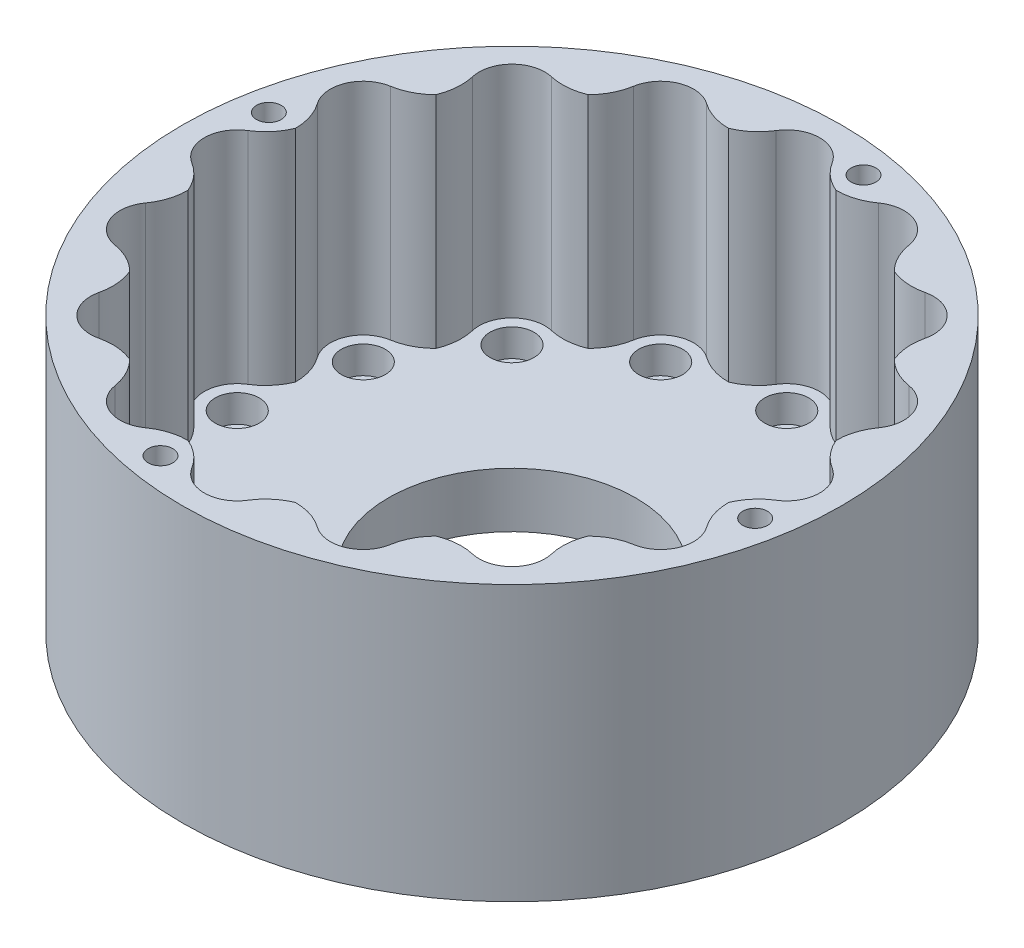
SolidWorks part; units mm, degrees
ref_plane "Front Plane" through (0, 0, 0) normal (0, 0, 1) x (1, 0, 0)
ref_plane "Top Plane" through (0, 0, 0) normal (0, 1, 0) x (1, 0, 0)
ref_plane "Right Plane" through (0, 0, 0) normal (1, 0, 0) x (0, 0, -1)
sketch "Sketch1" plane through (0, 0, 0) normal (0, 1, 0) x (1, 0, 0)
  arc A0 (-50.0283, 13.4631) -> (-51.515, 5.9892) centre (-1.875, 0) ccw
  arc A1 (4.1142, 49.64) -> (-7.8642, 49.64) centre (-1.875, 50) ccw
  arc A2 (-16.6515, 42.0695) -> (-16.6233, 42.0995) centre (-21.0092, 46.194) ccw
  arc A3 (-32.7408, 39.3358) -> (-41.2108, 30.8658) centre (-37.2303, 35.3553) ccw
  arc A4 (-45.4444, 24.5297) -> (-50.0283, 13.4631) centre (-48.069, 19.1342) ccw
  arc A5 (-51.515, 5.9892) -> (-51.515, -5.9892) centre (-51.875, 0) ccw
  arc A6 (-50.0283, -13.4631) -> (-45.4444, -24.5297) centre (-48.069, -19.1342) ccw
  arc A7 (-41.2108, -30.8658) -> (-32.7408, -39.3358) centre (-37.2303, -35.3553) ccw
  arc A8 (-26.4047, -43.5694) -> (-15.3381, -48.1533) centre (-21.0092, -46.194) ccw
  arc A9 (-7.8642, -49.64) -> (4.1142, -49.64) centre (-1.875, -50) ccw
  arc A10 (11.5881, -48.1533) -> (22.6547, -43.5694) centre (17.2592, -46.194) ccw
  arc A11 (28.9908, -39.3358) -> (37.4608, -30.8658) centre (33.4803, -35.3553) ccw
  arc A12 (40.4731, -14.5288) -> (40.4074, -14.5845) centre (44.319, -19.1342) ccw
  arc A13 (47.765, -5.9892) -> (47.765, 5.9892) centre (48.125, 0) ccw
  arc A14 (40.4074, 14.5845) -> (40.4731, 14.5288) centre (44.319, 19.1342) ccw
  arc A15 (37.4608, 30.8658) -> (28.9908, 39.3358) centre (33.4803, 35.3553) ccw
  arc A16 (22.6547, 43.5694) -> (11.5881, 48.1533) centre (17.2592, 46.194) ccw
  circle A17 centre (-1.875, 0) radius 60
  arc A18 (-41.2108, 30.8658) -> (-45.4444, 24.5297) centre (-1.875, 0) ccw
  arc A19 (-26.4047, 43.5694) -> (-32.7408, 39.3358) centre (-1.875, 0) ccw
  arc A20 (-15.3381, 48.1533) -> (-26.4047, 43.5694) centre (-21.0092, 46.194) ccw
  arc A21 (-7.8642, 49.64) -> (-15.3381, 48.1533) centre (-1.875, 0) ccw
  arc A22 (11.5881, 48.1533) -> (4.1142, 49.64) centre (-1.875, 0) ccw
  arc A23 (28.9908, 39.3358) -> (22.6547, 43.5694) centre (-1.875, 0) ccw
  arc A24 (41.6944, 24.5297) -> (37.4608, 30.8658) centre (-1.875, 0) ccw
  arc A25 (46.2783, 13.4631) -> (41.6944, 24.5297) centre (44.319, 19.1342) ccw
  arc A26 (46.2783, -13.4631) -> (47.765, -5.9892) centre (-1.875, 0) ccw
  arc A27 (41.6944, -24.5297) -> (46.2783, -13.4631) centre (44.319, -19.1342) ccw
  arc A28 (37.4608, -30.8658) -> (41.6944, -24.5297) centre (-1.875, 0) ccw
  arc A29 (-51.515, -5.9892) -> (-50.0283, -13.4631) centre (-1.875, 0) ccw
  arc A30 (-45.4444, -24.5297) -> (-41.2108, -30.8658) centre (-1.875, 0) ccw
  arc A31 (-32.7408, -39.3358) -> (-26.4047, -43.5694) centre (-1.875, 0) ccw
  arc A32 (-15.3381, -48.1533) -> (-7.8642, -49.64) centre (-1.875, 0) ccw
  arc A33 (-16.6233, -42.0995) -> (-16.6515, -42.0695) centre (-21.0092, -46.194) ccw
  arc A34 (4.1142, -49.64) -> (11.5881, -48.1533) centre (-1.875, 0) ccw
  arc A35 (22.6547, -43.5694) -> (28.9908, -39.3358) centre (-1.875, 0) ccw
  arc A36 (47.765, 5.9892) -> (46.2783, 13.4631) centre (-1.875, 0) ccw
  spline S0 degree 4 poles (44.0747, 11.4987) (44.2543, 11.2167) (44.5698, 10.6242) (44.9021, 9.6808) (45.0642, 8.3642) (44.9446, 7.1282) (44.593, 6.0249) (44.1211, 5.1947) (43.695, 4.5754) (43.3564, 4.0472) (43.0998, 3.6163) (42.8821, 3.198) (42.6994, 2.7973) (42.5503, 2.4153) (42.4301, 2.0557) (42.3415, 1.7357) (42.2778, 1.4587) (42.224, 1.1791) (42.1875, 0.9457) (42.1595, 0.7089) (42.1421, 0.4978) (42.1336, 0.3578) (42.1278, 0.2085) (42.1243, 0.037) (42.1247, -0.0678) (42.1293, -0.2634) (42.1379, -0.4367) (42.15, -0.5999) (42.1691, -0.7936) (42.1974, -1.0101) (42.2414, -1.2799) (42.3074, -1.6012) (42.4037, -1.9716) (42.5387, -2.3877) (42.6983, -2.7948) (42.8796, -3.1931) (43.1366, -3.6835) (43.482, -4.2594) (43.9287, -4.9065) (44.4091, -5.6745) (44.8007, -6.6105) (45.0295, -7.7093) (45.0295, -8.9484) (44.7352, -10.2696) (44.1902, -11.4212) (43.4619, -12.3657) (42.6206, -13.0778) (41.7593, -13.602) (40.7824, -14.2408) (39.77, -15.1062) (38.838, -16.2841) (38.1405, -17.7977) (37.8498, -19.2831) (37.8586, -20.6377) (38.0279, -21.8199) (38.2279, -22.8394) (38.2788, -23.9779) (38.0615, -25.1966) (37.5489, -26.4121) (36.7247, -27.5436) (35.7476, -28.3911) (34.706, -28.96) (33.6586, -29.2738) (32.6702, -29.405) (31.5286, -29.5836) (30.2595, -29.9481) (28.9262, -30.6268) (27.659, -31.7106) (26.7717, -32.9447) (26.2118, -34.1914) (25.9145, -35.2243) (25.7304, -35.9895) (25.5039, -36.7438) (25.1586, -37.555) (24.5413, -38.4785) (23.5696, -39.3957) (22.3328, -40.1097) (21.0527, -40.4927) (19.9443, -40.5655) (19.0691, -40.4589) (18.3026, -40.2779) (17.5479, -40.0547) (16.5047, -39.7958) (15.1451, -39.6573) (13.6327, -39.8087) (12.0605, -40.3642) (10.8061, -41.1795) (9.8558, -42.0964) (9.1304, -42.9957) (8.5226, -43.7861) (7.7271, -44.5363) (6.7136, -45.1539) (5.4911, -45.5763) (4.0991, -45.7244) (2.7902, -45.5605) (1.6261, -45.1394) (0.6656, -44.526) (-0.1173, -43.8431) (-1.0565, -43.1053) (-2.2252, -42.4205) (-3.657, -41.9295) (-5.3166, -41.7767) (-6.8026, -41.9949) (-8.0583, -42.439) (-9.1, -42.9656) (-9.9846, -43.4494) (-11.0219, -43.8219) (-12.2041, -43.9805) (-13.4901, -43.8751) (-14.8122, -43.455) (-15.9301, -42.7928) (-16.8127, -41.9651) (-17.4446, -41.0507) (-17.8788, -40.1387) (-18.4163, -39.084) (-19.1877, -37.9587) (-20.2985, -36.882) (-21.7915, -36.02) (-23.2794, -35.5964) (-24.6396, -35.491) (-25.8217, -35.5529) (-26.8286, -35.6328) (-27.9365, -35.5428) (-29.0946, -35.1922) (-30.227, -34.5552) (-31.2519, -33.6204) (-31.9862, -32.5593) (-32.4399, -31.4562) (-32.636, -30.3717) (-32.6594, -29.3636) (-32.7241, -28.1982) (-32.9674, -26.8887) (-33.5214, -25.4926) (-34.4835, -24.1318) (-35.6246, -23.1374) (-36.8021, -22.4676) (-37.9106, -22.0232) (-38.8934, -21.6866) (-39.9049, -21.1614) (-40.8517, -20.3639) (-41.648, -19.3123) (-42.2158, -18.0327) (-42.4612, -16.7628) (-42.4331, -15.5762) (-42.1811, -14.5123) (-41.8006, -13.5907) (-41.3845, -12.5128) (-41.0655, -11.2314) (-40.9867, -9.7374) (-41.2916, -8.0981) (-41.8623, -6.8333) (-42.485, -5.9251) (-43.0125, -5.3085) (-43.3736, -4.9275) (-43.7476, -4.5595) (-44.1231, -4.193) (-44.4829, -3.8105) (-44.8105, -3.3997) (-45.0744, -2.9955) (-45.2825, -2.6081) (-45.444, -2.2456) (-45.5676, -1.9138) (-45.6577, -1.6174) (-45.7221, -1.3598) (-45.7672, -1.1433) (-45.7981, -0.9691) (-45.8239, -0.7941) (-45.8419, -0.6396) (-45.8542, -0.5087) (-45.8622, -0.3996) (-45.8674, -0.31) (-45.8722, -0.1929) (-45.8754, -0.0484) (-45.8754, 0.057) (-45.8707, 0.2539) (-45.8614, 0.4217) (-45.8475, 0.5867) (-45.8289, 0.7543) (-45.8057, 0.9209) (-45.7778, 1.0866) (-45.7208, 1.3751) (-45.6162, 1.7824) (-45.4517, 2.2512) (-45.2056, 2.7679) (-44.9364, 3.2145) (-44.6596, 3.5954) (-44.3529, 3.9526) (-44.0247, 4.2897) (-43.6878, 4.6178) (-43.3537, 4.9489) (-43.036, 5.2844) (-42.7388, 5.6275) (-42.4647, 5.9787) (-42.2147, 6.3375) (-41.9285, 6.8032) (-41.6301, 7.388) (-41.2988, 8.2445) (-41.0869, 9.2182) (-41.0245, 10.1783) (-41.079, 10.9169) (-41.1306, 11.2832) (-41.1623, 11.4653) knots 0 0 0 0 0 0.00752 0.015039 0.022311 0.029582 0.03522 0.040858 0.043677 0.046496 0.049315 0.052134 0.054265 0.056396 0.058526 0.060657 0.061722 0.062788 0.064918 0.065984 0.067049 0.067582 0.068115 0.06918 0.070492 0.071149 0.071805 0.073033 0.074262 0.07549 0.076719 0.079176 0.081633 0.084089 0.086546 0.089003 0.09146 0.096539 0.101618 0.106697 0.111776 0.11923 0.126684 0.134323 0.141963 0.147625 0.153288 0.15895 0.164612 0.173852 0.183092 0.192408 0.201724 0.207559 0.213395 0.219231 0.225067 0.233024 0.240981 0.24862 0.25626 0.261858 0.267455 0.273053 0.278651 0.287828 0.297005 0.30639 0.315776 0.321674 0.327572 0.330521 0.33347 0.339368 0.347323 0.355277 0.363232 0.371186 0.377084 0.380033 0.382982 0.38888 0.394778 0.404164 0.413549 0.422726 0.431904 0.437501 0.443099 0.448697 0.454294 0.461934 0.469574 0.477531 0.485487 0.491323 0.497159 0.502995 0.508831 0.518146 0.527462 0.536702 0.545942 0.551604 0.557267 0.562929 0.568591 0.576231 0.58387 0.591691 0.599511 0.605182 0.610853 0.616525 0.622196 0.631785 0.641374 0.650964 0.660553 0.666224 0.671895 0.677566 0.683238 0.691058 0.698878 0.706518 0.714157 0.71982 0.725482 0.731145 0.736807 0.746047 0.755287 0.764602 0.773918 0.779754 0.78559 0.791426 0.797261 0.805218 0.813175 0.820815 0.828454 0.834052 0.83965 0.845248 0.850845 0.860022 0.869199 0.878585 0.887971 0.89092 0.893869 0.896818 0.899767 0.902716 0.905665 0.908614 0.911563 0.913551 0.91554 0.917528 0.919517 0.920511 0.921506 0.9225 0.923494 0.924489 0.924986 0.925483 0.92598 0.926477 0.927472 0.928416 0.929361 0.930305 0.931249 0.932194 0.933138 0.934083 0.935027 0.938805 0.942583 0.945226 0.947869 0.950513 0.953156 0.955799 0.958442 0.961086 0.963729 0.966185 0.968641 0.971097 0.973554 0.978466 0.983378 0.991689 0.995845 1 1 1 1 1 construction
  spline S1 degree 4 poles (40.4731, -14.5288) (40.4566, -14.5426) (40.4402, -14.5565) (40.4237, -14.5705) (40.4074, -14.5845) knots 0.165033 0.165033 0.165033 0.165033 0.165033 0.165518 0.165518 0.165518 0.165518 0.165518
  spline S2 degree 4 poles (40.4731, 14.5288) (40.4566, 14.5426) (40.4402, 14.5565) (40.4237, 14.5705) (40.4074, 14.5845) knots 0.165033 0.165033 0.165033 0.165033 0.165033 0.165518 0.165518 0.165518 0.165518 0.165518
  spline S3 degree 4 poles (-16.6233, 42.0995) (-16.6304, 42.0921) (-16.6375, 42.0846) (-16.6445, 42.0771) (-16.6515, 42.0695) knots 0.600544 0.600544 0.600544 0.600544 0.600544 0.600775 0.600775 0.600775 0.600775 0.600775
  dimension "D1" = 16
extrude "Boss-Extrude1" add sketch "Sketch1" along normal blind 50 contours A17 | A26 A13 A36 A25 A24 A15 A23 A16 A22 A1 A21 A20 A19 A3 A18 A4 A0 A5 A29 A6 A30 A7 A31 A8 A32 A9 A34 A10 A35 A11 A28 A27
sketch "Sketch3" plane through (0, 0, 0) normal (0, 1, 0) x (1, 0, 0)
  circle A0 centre (-1.875, 0) radius 60
extrude "Boss-Extrude2" add sketch "Sketch3" along normal blind 10
fillet "Fillet1" radius 10 2 edges at (11.5881, 30, -48.1533) (4.1142, 30, -49.64)
fillet "Fillet2" radius 10 30 edges at (-50.0283, 30, -13.4631) (-51.515, 30, -5.9892) (-51.515, 30, 5.9892) (-50.0283, 30, 13.4631) (-45.4444, 30, 24.5297) (-41.2108, 30, 30.8658) (-32.7408, 30, 39.3358) (-26.4047, 30, 43.5694) (-15.3381, 30, 48.1533) (-7.8642, 30, 49.64) (-45.4444, 30, -24.5297) (-41.2108, 30, -30.8658) (-32.7408, 30, -39.3358) (-26.4047, 30, -43.5694) (-7.8642, 30, -49.64) (-15.3381, 30, -48.1533) (4.1142, 30, 49.64) (11.5881, 30, 48.1533) (22.6547, 30, 43.5694) (28.9908, 30, 39.3358) (37.4608, 30, 30.8658) (41.6944, 30, 24.5297) (46.2783, 30, 13.4631) (47.765, 30, 5.9892) (47.765, 30, -5.9892) (46.2783, 30, -13.4631) (41.6944, 30, -24.5297) (37.4608, 30, -30.8658) (28.9908, 30, -39.3358) (22.6547, 30, -43.5694)
sketch "Sketch5" plane through (0, 50, 0) normal (0, 1, 0) x (1, 0, 0)
  circle A0 centre (-11.7359, -54.1088) radius 2.25
  circle A3 centre (-55.9838, 9.8609) radius 2.25
  circle A4 centre (7.9859, 54.1088) radius 2.25
  circle A5 centre (52.2338, -9.8609) radius 2.25
  point P12 (-1.875, 0)
  dimension "D1" = 4
extrude "Cut-Extrude2" cut sketch "Sketch5" against normal blind 6.1 contours A4 | A3 | A0 | A5 region at (7.9859, 50, -54.1088)
sketch "Sketch6" plane through (0, 10, 0) normal (0, 1, 0) x (1, 0, 0)
  circle A0 centre (-1.875, 0) radius 50 construction
  circle A1 centre (-1.875, 50) radius 4
  circle A2 centre (17.2592, 46.194) radius 4
  circle A3 centre (33.4803, 35.3553) radius 4
  circle A4 centre (44.319, 19.1342) radius 4
  circle A5 centre (48.125, 0) radius 4
  circle A6 centre (44.319, -19.1342) radius 4
  circle A7 centre (33.4803, -35.3553) radius 4
  circle A8 centre (17.2592, -46.194) radius 4
  circle A9 centre (-1.875, -50) radius 4
  circle A10 centre (-21.0092, -46.194) radius 4
  circle A11 centre (-37.2303, -35.3553) radius 4
  circle A12 centre (-48.069, -19.1342) radius 4
  circle A13 centre (-51.875, 0) radius 4
  circle A14 centre (-48.069, 19.1342) radius 4
  circle A15 centre (-37.2303, 35.3553) radius 4
  circle A16 centre (-21.0092, 46.194) radius 4
  dimension "D1" = 16
extrude "Cut-Extrude3" cut sketch "Sketch6" against normal blind 5
sketch "Sketch7" plane through (0, 0, 0) normal (0, -1, 0) x (1, 0, 0)
  circle A1 centre (-1.875, 0) radius 22.5
  point P0 (-1.875, 0)
  dimension "D1" = 45
extrude "Cut-Extrude4" cut sketch "Sketch7" against normal blind 10
